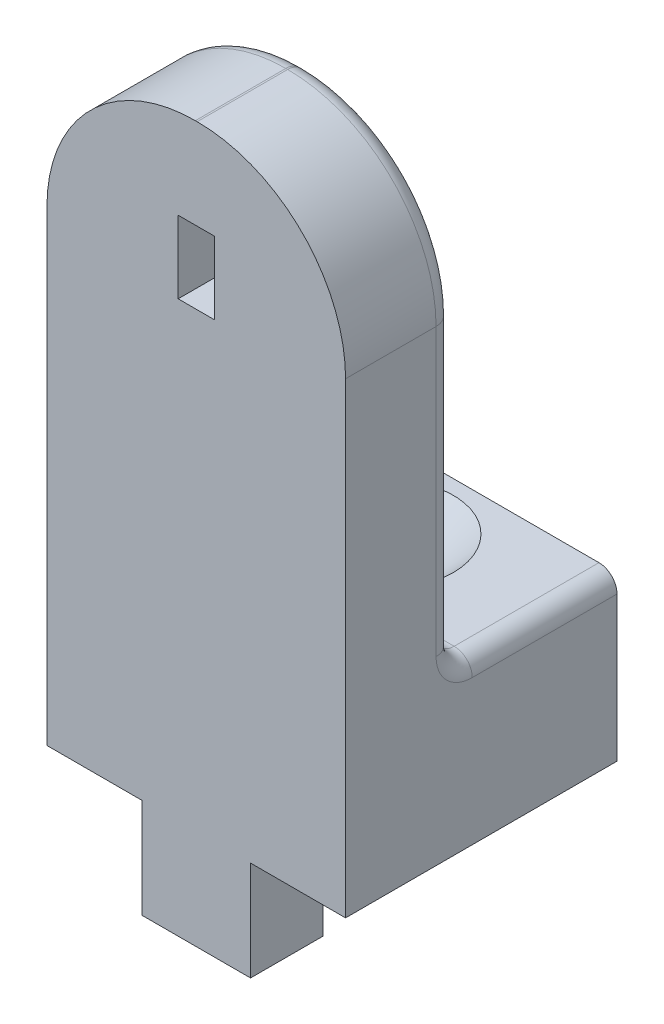
SolidWorks part; units mm, degrees
ref_plane "Front Plane" through (0, 0, 0) normal (0, 0, 1) x (1, 0, 0)
ref_plane "Top Plane" through (0, 0, 0) normal (0, 1, 0) x (1, 0, 0)
ref_plane "Right Plane" through (0, 0, 0) normal (1, 0, 0) x (0, 0, -1)
sketch "Sketch1" plane through (0, 0, 0) normal (0, 1, 0) x (1, 0, 0)
  line L1 (-8.25, 7.5) -> (8.25, 7.5)
  line L2 (-8.25, 7.5) -> (-8.25, -7.5)
  line L3 (-8.25, -7.5) -> (8.25, -7.5)
  line L4 (8.25, 7.5) -> (8.25, -7.5)
  line L5 (-8.25, 7.5) -> (8.25, -7.5) construction
  line L6 (-8.25, -7.5) -> (8.25, 7.5) construction
  circle A0 centre (0, 3) radius 2.2
  point P0 (0, 0)
  dimension "D3" = 4.4
  dimension "D1" = 16.5
  dimension "D2" = 15
  dimension "D4" = 4.5
extrude "Boss-Extrude1" add sketch "Sketch1" along normal blind 9
chamfer "Chamfer1" distance 1.5 angle 45 1 edges at (0, 9, -0.8)
sketch "Sketch2" plane through (0, 9, 0) normal (0, 1, 0) x (1, 0, 0)
  line L0 (-8.25, 7.5) -> (-8.25, -7.5) construction
  line L1 (-8.25, -1.5) -> (8.25, -1.5)
  line L2 (-8.25, -1.5) -> (-8.25, -7.5)
  line L3 (-8.25, -7.5) -> (8.25, -7.5)
  line L4 (8.25, -1.5) -> (8.25, -7.5)
  line L5 (8.25, -7.5) -> (8.25, 7.5) construction
  dimension "D1" = 6
extrude "Boss-Extrude2" add sketch "Sketch2" along normal blind 25
sketch "Sketch4" plane through (0, 0, 1.5) normal (0, 0, -1) x (-1, 0, 0)
  line L0 (0, 25) -> (0, 29) construction
  line L1 (-1, 29) -> (1, 29)
  line L2 (-1, 29) -> (-1, 25)
  line L3 (-1, 25) -> (1, 25)
  line L4 (1, 29) -> (1, 25)
  line L5 (-8.25, 34) -> (8.25, 34) construction
  line L6 (-2, 30) -> (2, 30)
  line L7 (2, 30) -> (2, 24)
  line L8 (-2, 24) -> (2, 24)
  line L9 (-2, 30) -> (-2, 24)
  dimension "D1" = 2
  dimension "D2" = 4
  dimension "D3" = 5
  dimension "D4" = 1
extrude "Cut-Extrude2" cut sketch "Sketch4" against normal through all both contours L0 L3 L4 L1 | L3 L0 L1 L2 region at (0.5, 27, 1.5) region at (-0.5, 27, 1.5)
extrude "Cut-Extrude3" cut sketch "Sketch4<3>" against normal blind 1 contours L6 L9 L8 L7 L1 L4 L3 L2 region at (0, 29.9279, 1.5)
sketch "Sketch4<3>" plane through (0, 0, 1.5) normal (0, 0, -1) x (-1, 0, 0) same geometry as "Sketch4"
fillet "Fillet1" radius 1 6 edges at (8.25, 21.5, 1.5) (-8.25, 9, -3) (0, 34, 1.5) (8.25, 9, -3) (-8.25, 21.5, 1.5) (0, 9, 1.5)
sketch "Sketch7" plane through (0, 0, 2.5) normal (0, 0, -1) x (-1, 0, 0)
  line L0 (-2, 30) -> (-2, 24) construction
  line L1 (-2, 25) -> (2, 25)
  line L2 (-2, 25) -> (-2, 24)
  line L3 (-2, 24) -> (2, 24)
  line L4 (2, 25) -> (2, 24)
  line L5 (-1, 25) -> (1, 25) construction
extrude "Boss-Extrude4" add sketch "Sketch7" along normal blind 1
fillet "Fillet2" radius 8.2 4 edges at (7.9571, 33.7071, 1.7929) (-7.9571, 33.7071, 1.7929) (-8.25, 34, 5) (8.25, 34, 5)
sketch "Sketch8" plane through (0, 0, 0) normal (0, -1, 0) x (1, 0, 0)
  line L0 (0, 0) -> (0, -50000) construction
  line L1 (-8.25, 7.5) -> (8.25, 7.5) construction
  line L2 (-3, 7.5) -> (3, 7.5)
  line L3 (-3, 7.5) -> (-3, 3.5)
  line L4 (-3, 3.5) -> (3, 3.5)
  line L5 (3, 7.5) -> (3, 3.5)
  line L6 (-3, 7.5) -> (3, 3.5) construction
  line L7 (-3, 3.5) -> (3, 7.5) construction
  point P3 (0, 5.5)
  point P10 (0, 0)
  dimension "D1" = 6
  dimension "D2" = 4
extrude "Boss-Extrude5" add sketch "Sketch8" along normal blind 5.5
